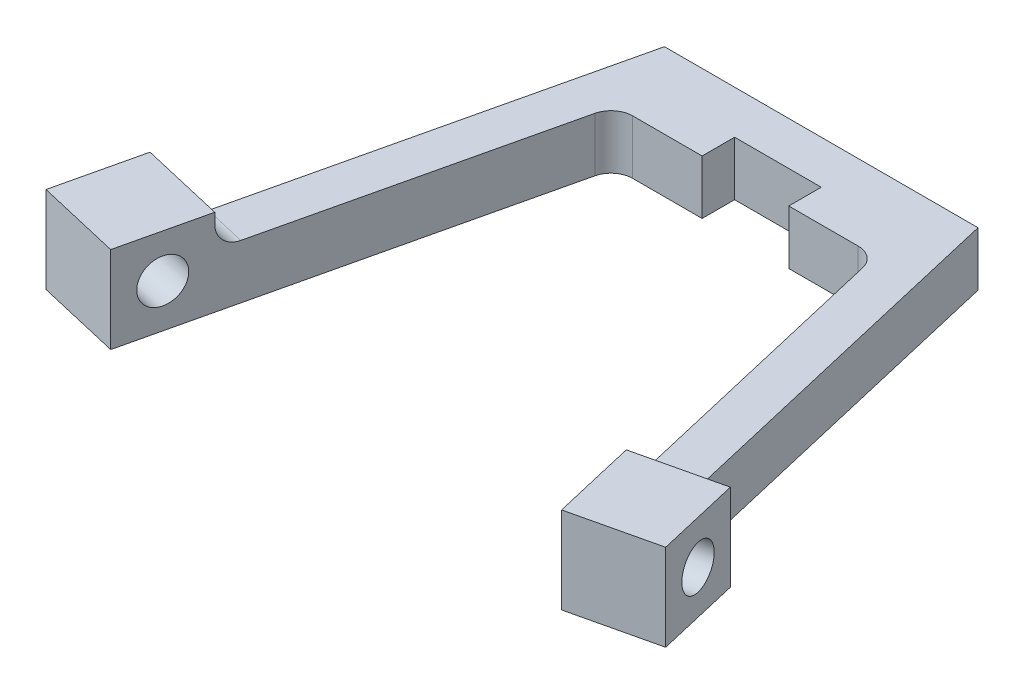
SolidWorks part; units mm, degrees
ref_plane "Front Plane" through (0, 0, 0) normal (0, 0, 1) x (1, 0, 0)
ref_plane "Top Plane" through (0, 0, 0) normal (0, 1, 0) x (1, 0, 0)
ref_plane "Right Plane" through (0, 0, 0) normal (1, 0, 0) x (0, 0, -1)
sketch "Sketch1" plane through (0, 0, 0) normal (0, 1, 0) x (1, 0, 0)
  line L0 (-12, 0) -> (12, 0)
  line L1 (12, 0) -> (19, -30)
  line L2 (0, 0) -> (0, -32.241) construction
  line L3 (-12, 0) -> (-19, -30)
  dimension "D1" = 12
  dimension "D2" = 19
  dimension "D3" = 30
extrude "Extrude-Thin1" add sketch "Sketch1" along normal blind 5 thin thin type one direction wall 4
sketch "Sketch2" plane through (-11.3804, 0, -2.6554) normal (0.9738, 0, 0.2272) x (0.2272, 0, -0.9738)
  line L1 (-33.5326, 8) -> (-41.5326, 8)
  line L2 (-33.5326, 8) -> (-33.5326, 0)
  line L3 (-33.5326, 0) -> (-41.5326, 0)
  line L4 (-41.5326, 8) -> (-41.5326, 0)
  line L5 (-2.7268, 0) -> (-33.5326, 0) construction
  line L6 (-33.5326, 5) -> (-33.5326, 0) construction
  dimension "D1" = 8
  dimension "D2" = 8
extrude "Boss-Extrude1" add sketch "Sketch2" against normal blind 8
sketch "Sketch3" plane through (-11.3804, 0, -2.6554) normal (0.9738, 0, 0.2272) x (0.2272, 0, -0.9738)
  line L0 (-37.5326, 8) -> (-37.5326, 0) construction
  line L1 (-33.5326, 8) -> (-41.5326, 8) construction
  line L4 (-2.7268, 0) -> (-41.5326, 0) construction
  circle A0 centre (-37.5326, 4) radius 2
  point P4 (-42.1805, 0)
  dimension "D1" = 4
extrude "Cut-Extrude1" cut sketch "Sketch3" against normal through all
mirror "Mirror1" about plane through (0, 0, 0) normal (1, 0, 0) of "Cut-Extrude1", "Boss-Extrude1"
fillet "Fillet1" radius 2 6 edges at (12, 2.5, 0) (-12, 2.5, 0) (-22.8954, 2.5, 29.0911) (-20.9477, 5, 29.5455) (22.8954, 2.5, 29.0911) (20.9477, 5, 29.5455)
sketch "Sketch4" plane through (0, 0, 0) normal (0, 0, 1) x (1, 0, 0)
  line L0 (10.4129, 0) -> (-10.4129, 0) construction
  line L1 (-4, 5) -> (4, 5)
  line L2 (-4, 5) -> (-4, 0)
  line L3 (-4, 0) -> (4, 0)
  line L4 (4, 5) -> (4, 0)
  line L5 (-4, 5) -> (4, 0) construction
  line L6 (-4, 0) -> (4, 5) construction
  line L7 (10.4129, 5) -> (-10.4129, 5) construction
  point P0 (0, 2.5)
  point P9 (0, 0)
  dimension "D1" = 8
extrude "Cut-Extrude2" cut sketch "Sketch4" against normal blind 3
sketch "Sketch6" plane through (0, 5, 0) normal (0, 1, 0) x (1, 0, 0)
  line L0 (-15.1741, 4) -> (-14.4741, 7)
  line L1 (-14.4741, 7) -> (14.4741, 7)
  line L2 (14.4741, 7) -> (15.1741, 4)
  line L3 (15.1741, 4) -> (-15.1741, 4)
  line L4 (-15.1741, 4) -> (-22.4409, -27.1434) construction
  line L5 (22.4409, -27.1434) -> (15.1741, 4) construction
  dimension "D1" = 3
extrude "Boss-Extrude2" add sketch "Sketch6" against normal up to surface (5 mm away) up to face at (0, 0, 15.2429)
